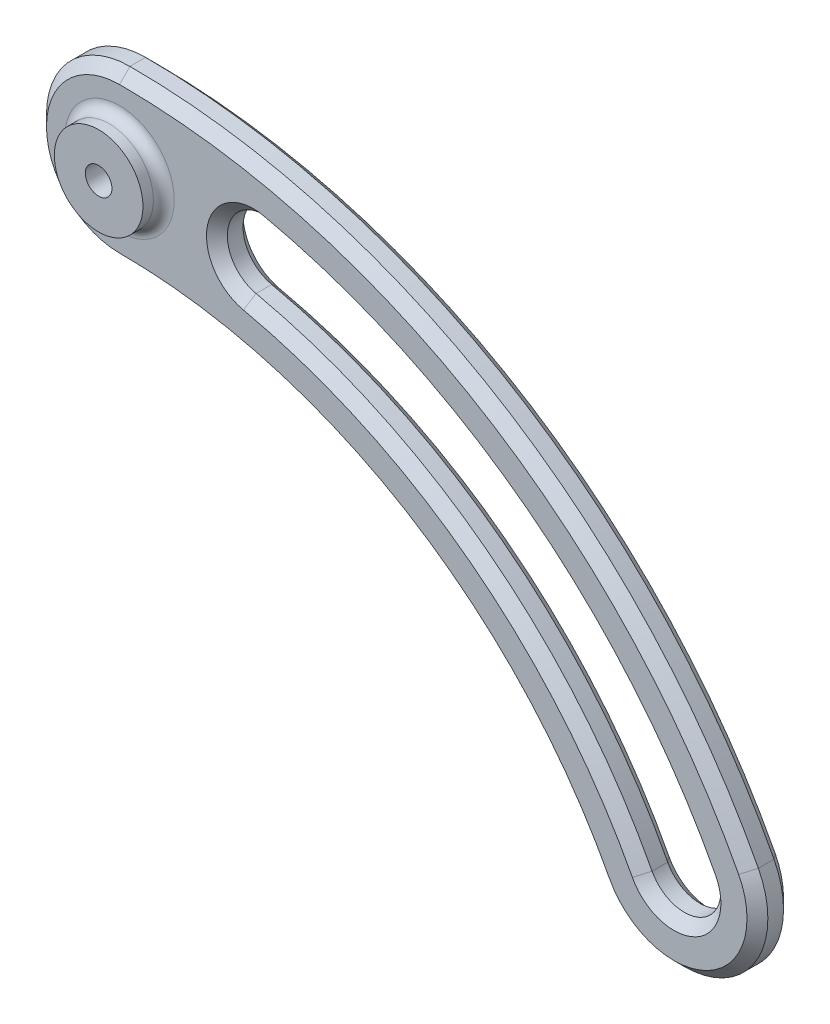
SolidWorks part; units mm, degrees
material "ABS"
ref_plane "Front Plane" through (0, 0, 0) normal (0, 0, 1) x (1, 0, 0)
ref_plane "Top Plane" through (0, 0, 0) normal (0, 1, 0) x (1, 0, 0)
ref_plane "Right Plane" through (0, 0, 0) normal (1, 0, 0) x (0, 0, -1)
sketch "Sketch1" plane through (0, 0, 0) normal (0, 0, 1) x (1, 0, 0)
  line L0 (0, 0) -> (0, -120) construction
  line L1 (0, -120) -> (112.7631, -78.9576) construction
  line L4 (25.676, -2.7791) -> (0, -120) construction
  line L5 (106.3006, -64.3208) -> (0, -120) construction
  circle A0 centre (0, 0) radius 2.55
  circle A1 centre (0, 0) radius 8.5
  arc A2 (92.1272, -71.7447) -> (120.474, -56.8969) centre (106.3006, -64.3208) ccw
  arc A3 (0, 16) -> (0, -16) centre (0, 0) ccw
  arc A4 (112.7631, -78.9576) -> (0, 0) centre (0, -120) ccw construction
  arc A5 (100.0998, -67.5687) -> (112.5015, -61.0728) centre (106.3006, -64.3208) ccw
  arc A6 (27.1737, 4.0588) -> (24.1782, -9.617) centre (25.676, -2.7791) ccw
  arc A8 (100.0998, -67.5687) -> (24.1782, -9.617) centre (0, -120) ccw
  arc A9 (112.5015, -61.0728) -> (27.1737, 4.0588) centre (0, -120) ccw
  arc A10 (120.474, -56.8969) -> (0, 16) centre (0, -120) ccw
  arc A11 (92.1272, -71.7447) -> (0, -16) centre (0, -120) ccw
  dimension "D1" = 5.1
  dimension "D2" = 17
  dimension "D3" = 7
  dimension "D4" = 16
  dimension "D5" = 50
  dimension "D6" = 120
  dimension "D7" = 70
extrude "Boss-Extrude1" add sketch "Sketch1" along normal blind 7 contours A11 A2 A10 A3 A1 A9 A5 A8 A6 | A1 A0 region at (-8.2596, 0, 0) region at (56.1772, -23.4396, 0)
extrude "Boss-Extrude2" add sketch "Sketch1<3>" along normal blind 4 from surface contours A1 | A0 starting at face at (55.4925, -28.2895, 7)
sketch "Sketch1<3>" plane through (0, 0, 0) normal (0, 0, 1) x (1, 0, 0) same geometry as "Sketch1"
chamfer "Chamfer1" distance 2 angle 45 16 edges at (-16, 0, 7) (53.8398, -31.0209, 7) (70.4059, -3.6427, 7) (113.7245, -78.4942, 7) (-16, 0, 0) (53.8398, -31.0209, 0) (70.4059, -3.6427, 0) (113.7245, -78.4942, 0) (18.8381, -1.2813, 0) (68.5628, -30.1771, 0) (77.0573, -19.0486, 0) (109.5486, -70.5216, 0) (68.5628, -30.1771, 7) (109.5486, -70.5216, 7) (18.8381, -1.2813, 7) (77.0573, -19.0486, 7)
fillet "Fillet2" radius 2 1 edges at (8.5, 0, 7)
sketch "Sketch2" plane through (0, 0, 11) normal (0, 0, 1) x (1, 0, 0)
  circle A0 centre (0, 0) radius 5.25
  dimension "D1" = 10.5
extrude "Cut-Extrude1" cut sketch "Sketch2" against normal up to surface (11 mm away) from offset 9 contours A0 up to face at (55.7606, -27.8465, 0) offset against normal yes
ref_plane "Plane2" through (0, 0, 3.5) normal (0, 0, -1) x (-1, 0, 0)
sketch "Sketch10" plane through (0, 0, 3.5) normal (0, 0, -1) x (-1, 0, 0)
  line L0 (-77.0573, -19.0486) -> (-68.5628, -30.1771) construction
  arc A0 (-27.1737, 4.0588) -> (-112.5015, -61.0728) centre (0, -120) ccw construction
  arc A1 (-24.1782, -9.617) -> (-100.0998, -67.5687) centre (0, -120) ccw construction
  arc A2 (-25.676, -2.7791) -> (-106.3006, -64.3208) centre (0, -120) ccw construction
  point P0 (-106.3006, -64.3208)
  point P1 (-25.676, -2.7791)
  point P13 (-72.81, -24.6129)
ref_plane "Plane1" [suppressed] through (49.3228, -94.1652, 0) normal (0.464, -0.8858, 0) x (-0.8858, -0.464, 0)
ref_axis "Axis1" through (106.3006, -64.3208, 5) along (0, 0, -1)
sketch "Sketch3" [suppressed] plane through (49.3228, -94.1652, 0) normal (0.464, -0.8858, 0) x (-0.8858, -0.464, 0)
  line L2 (-73.3208, 0) -> (-71.3208, -2) construction
  line L3 (-57.3208, -2) -> (-55.3208, 0) construction
  line L4 (-57.3208, -5) -> (-57.3208, -2) construction
  line L5 (-55.3208, -7) -> (-57.3208, -5) construction
  line L6 (-64.3208, -5) -> (-64.3208, -2) construction
  line L9 (-57.3208, -2) -> (-55.3208, 0) construction
  line L10 (-57.3208, -5) -> (-57.3208, -2) construction
  line L11 (-55.3208, -7) -> (-57.3208, -5) construction
  line L12 (-55.8511, -7.5303) -> (-58.0708, -5.3107)
  line L13 (-58.0708, -5.3107) -> (-58.0708, -1.6893)
  line L14 (-58.0708, -1.6893) -> (-56.3814, 0)
  line L18 (-56.3814, 0) -> (-64.3208, 0)
  line L20 (-58.0708, -1.6893) -> (-55.8511, 0.5303) construction
  line L21 (-64.3208, -7.5303) -> (-55.8511, -7.5303)
  line L22 (-64.3208, -7.5303) -> (-64.3208, 0)
  dimension "D1" = 0.75
revolve "Revolve1" [suppressed] add sketch "Sketch3" angle 360 about axis through (106.3006, -64.3208, 5) along (0, 0, -1)
chamfer "Chamfer2" [suppressed] distance 0.75 angle 60
fillet "Fillet3" [suppressed] radius 0.5
sketch "Sketch4" [suppressed] plane through (0, 0, 7.5303) normal (0, 0, 1) x (1, 0, 0)
  circle A1 centre (106.3006, -64.3208) radius 8.4697
  circle A2 centre (106.3006, -64.3208) radius 8.4697
  dimension "D1" = 0
extrude "Boss-Extrude4" [suppressed] add sketch "Sketch4" along normal up to surface (3.4697 mm away)
sketch "Sketch5" [suppressed] plane through (0, 0, 11) normal (0, 0, 1) x (1, 0, 0)
  circle A0 centre (106.3006, -64.3208) radius 2.55
  dimension "D1" = 5.1
extrude "Cut-Extrude2" [suppressed] cut sketch "Sketch5" against normal up to surface (11 mm away)
sketch "Sketch7" plane through (0, 0, 2) normal (0, 0, -1) x (-1, 0, 0)
  circle A0 centre (0, 0) radius 2.55 construction
  circle A1 centre (0, 0) radius 2.55
extrude "Printed Bridging Diaphragm" [suppressed] add sketch "Sketch7" against normal blind 0.5
sketch "Sketch8" plane through (0, 0, 0) normal (0, 0, -1) x (-1, 0, 0)
  arc A0 (10.4286, -9.3405) -> (10.4286, 9.3405) centre (14, 0) ccw
  arc A1 (0, -14) -> (0, 14) centre (0, 0) ccw construction
  arc A2 (-119.4136, -69.2249) -> (-102.8652, -77.8927) centre (-112.7965, -76.7225) ccw
  arc A3 (-118.7024, -57.8249) -> (-93.8989, -70.8167) centre (-106.3006, -64.3208) ccw construction
  arc A4 (-119.4136, -69.2249) -> (-102.8652, -77.8927) centre (-106.3006, -64.3208) ccw
  arc A5 (10.4286, -9.3405) -> (10.4286, 9.3405) centre (0, 0) ccw
  dimension "D1" = 10
  dimension "D2" = 10
extrude "Printed Hold Down Tabls" [suppressed] add sketch "Sketch8" against normal blind 0.5
ref_axis "Axis2" through (0, 0, 11) along (0, 0, -1)
